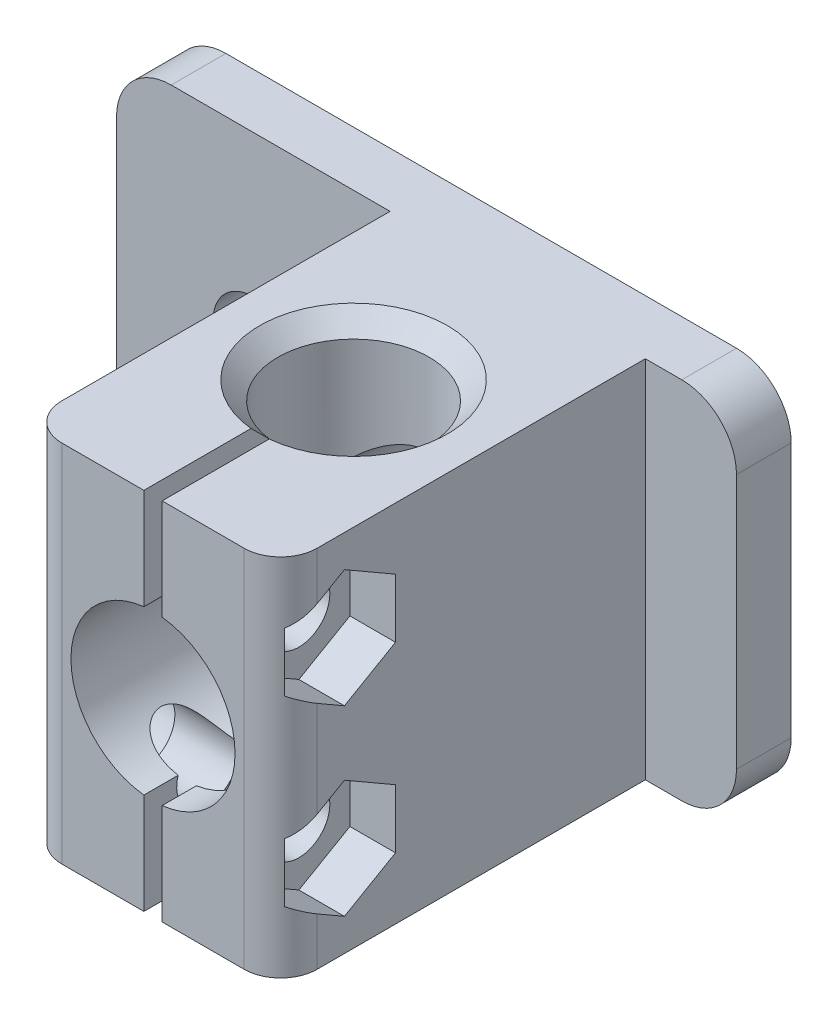
SolidWorks part; units mm, degrees
material "ABS"
ref_plane "Front Plane" through (0, 0, 0) normal (0, 0, 1) x (1, 0, 0)
ref_plane "Top Plane" through (0, 0, 0) normal (0, 1, 0) x (1, 0, 0)
ref_plane "Right Plane" through (0, 0, 0) normal (1, 0, 0) x (0, 0, -1)
sketch "Sketch1" plane through (0, 0, 0) normal (0, 0, 1) x (1, 0, 0)
  line L1 (-17, -10) -> (17, -10)
  line L2 (-17, -10) -> (-17, 10)
  line L3 (-17, 10) -> (17, 10)
  line L4 (17, -10) -> (17, 10)
  line L5 (-17, -10) -> (17, 10) construction
  line L6 (-17, 10) -> (17, -10) construction
  point P0 (0, 0)
  dimension "D1" = 20
  dimension "D2" = 34
extrude "Boss-Extrude1" add sketch "Sketch1" along normal blind 3
fillet "Fillet1" radius 3 4 edges at (17, -10, 1.5) (-17, -10, 1.5) (-17, 10, 1.5) (17, 10, 1.5)
sketch "Sketch2" plane through (0, 0, 3) normal (0, 0, 1) x (1, 0, 0)
  line L0 (14, 10) -> (-14, 10) construction
  line L1 (12, 10) -> (-2, 10)
  line L2 (12, 10) -> (12, -10)
  line L3 (12, -10) -> (-2, -10)
  line L4 (-2, 10) -> (-2, -10)
  line L5 (-14, -10) -> (14, -10) construction
  line L6 (17, -7) -> (17, 7) construction
  dimension "D1" = 14
  dimension "D2" = 5
extrude "Boss-Extrude2" add sketch "Sketch2" along normal blind 20
sketch "Sketch3" plane through (0, 10, 0) normal (0, 1, 0) x (1, 0, 0)
  line L0 (5, -12) -> (5, -23) construction
  line L1 (12, -23) -> (-2, -23) construction
  line L2 (4.5, -16.1198) -> (4.5, -23)
  line L3 (5.5, -16.1198) -> (5.5, -23)
  line L4 (4.5, -23) -> (5.5, -23)
  line L5 (14, 0) -> (-14, 0) construction
  arc A0 (5.5, -16.1198) -> (4.5, -16.1198) centre (5, -12) ccw
  dimension "D1" = 8.3
  dimension "D2" = 12
  dimension "D3" = 1
extrude "Cut-Extrude1" cut sketch "Sketch3" against normal through all
chamfer "Chamfer1" distance 1 angle 45 2 edges at (5, -10, 7.85) (5, 10, 7.85)
sketch "Sketch4" plane through (0, 0, 3) normal (0, 0, 1) x (1, 0, 0)
  line L0 (-2, 10) -> (-14, 10) construction
  line L1 (-17, 7) -> (-17, -7) construction
  circle A0 centre (-9.5, 0) radius 2.2
  point P4 (-8, 10)
  dimension "D1" = 4.4
  dimension "D2" = 10
  dimension "D3" = 7.5
extrude "Cut-Extrude2" cut sketch "Sketch4" against normal through all
sketch "Sketch5" plane through (12, 0, 0) normal (1, 0, 0) x (0, 0, -1)
  line L0 (0, -7) -> (0, 7) construction
  line L1 (-19.5, 5) -> (-19.5, -5) construction
  line L2 (-19.5, 0) -> (-23, 0) construction
  line L3 (-23, -10) -> (-23, 10) construction
  circle A0 centre (-19.5, 5) radius 1.7
  circle A1 centre (-19.5, -5) radius 1.7
  dimension "D1" = 3.4
  dimension "D2" = 10
  dimension "D3" = 19.5
extrude "Cut-Extrude3" cut sketch "Sketch5" against normal through all
fillet "Fillet2" radius 2 2 edges at (12, 0, 23) (-2, 0, 23)
sketch "Sketch6" plane through (12, 0, 0) normal (1, 0, 0) x (0, 0, -1)
  line L1 (-16.7, 3.3834) -> (-16.7, 6.6166)
  line L2 (-16.7, 6.6166) -> (-19.5, 8.2332)
  line L3 (-19.5, 8.2332) -> (-22.3, 6.6166)
  line L4 (-22.3, 6.6166) -> (-22.3, 3.3834)
  line L5 (-22.3, 3.3834) -> (-19.5, 1.7668)
  line L6 (-19.5, 1.7668) -> (-16.7, 3.3834)
  line L7 (-16.7, -3.3834) -> (-19.5, -1.7668)
  line L8 (-19.5, -1.7668) -> (-22.3, -3.3834)
  line L9 (-22.3, -3.3834) -> (-22.3, -6.6166)
  line L10 (-22.3, -6.6166) -> (-19.5, -8.2332)
  line L11 (-19.5, -8.2332) -> (-16.7, -6.6166)
  line L12 (-16.7, -6.6166) -> (-16.7, -3.3834)
  circle A0 centre (-19.5, 5) radius 2.8 construction
  circle A1 centre (-19.5, -5) radius 2.8 construction
  dimension "D1" = 5.6
extrude "Cut-Extrude4" cut sketch "Sketch6" against normal blind 2.5
sketch "Sketch7" plane through (-2, 0, 0) normal (-1, 0, 0) x (0, 0, 1)
  circle A0 centre (19.5, 5) radius 2.75
  circle A1 centre (19.5, -5) radius 2.75
  dimension "D1" = 5.5
extrude "Cut-Extrude5" cut sketch "Sketch7" against normal blind 3
sketch "Sketch8" plane through (0, 0, 23) normal (0, 0, 1) x (1, 0, 0)
  line L0 (-9.5, 0) -> (5, 0) construction
  circle A0 centre (5, 0) radius 2.2
  circle A1 centre (-9.5, 0) radius 2.2 construction
  dimension "D1" = 14.5
extrude "Cut-Extrude6" cut sketch "Sketch8" against normal through all
sketch "Sketch9" plane through (0, 0, 23) normal (0, 0, 1) x (1, 0, 0)
  circle A0 centre (5, 0) radius 4.5
  dimension "D1" = 9
extrude "Cut-Extrude7" cut sketch "Sketch9" against normal blind 21
